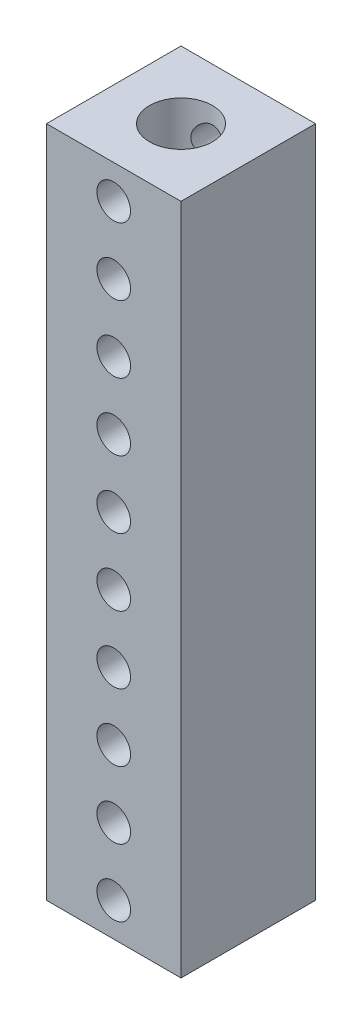
SolidWorks part; units mm, degrees
ref_plane "Front Plane" through (0, 0, 0) normal (0, 0, 1) x (1, 0, 0)
ref_plane "Top Plane" through (0, 0, 0) normal (0, 1, 0) x (1, 0, 0)
ref_plane "Right Plane" through (0, 0, 0) normal (1, 0, 0) x (0, 0, -1)
sketch "Sketch1" plane through (0, 0, 0) normal (0, 1, 0) x (1, 0, 0)
  line L1 (-10, 10) -> (10, 10)
  line L2 (-10, 10) -> (-10, -10)
  line L3 (-10, -10) -> (10, -10)
  line L4 (10, 10) -> (10, -10)
  line L5 (-10, 10) -> (10, -10) construction
  line L6 (-10, -10) -> (10, 10) construction
  circle A0 centre (0, 0) radius 4.6831
  point P0 (0, 0)
  dimension "D1" = 20
  dimension "D2" = 20
extrude "Boss-Extrude1" add sketch "Sketch1" along normal blind 100
sketch "Sketch2" plane through (0, 0, 10) normal (0, 0, 1) x (1, 0, 0)
  line L0 (-10, 0) -> (10, 0) construction
  circle A0 centre (0, 5) radius 2.5
  dimension "D1" = 5
  dimension "D2" = 5
extrude "Cut-Extrude1" cut sketch "Sketch2" against normal blind 100
pattern_linear "LPattern1" count 8 spacing 10 along (0, 1, 0) of "Cut-Extrude1"
sketch "Sketch3" plane through (0, 0, 10) normal (0, 0, 1) x (1, 0, 0)
  line L0 (0, -900) -> (0, 49100) construction
  line L1 (-10, 100) -> (10, 100) construction
  circle A0 centre (0, 95) radius 2.5
  circle A1 centre (0, 85) radius 2.5
  point P5 (0, 100)
  dimension "D1" = 5
  dimension "D2" = 5
  dimension "D3" = 5
  dimension "D4" = 15
extrude "Cut-Extrude4" cut sketch "Sketch3" against normal through all
